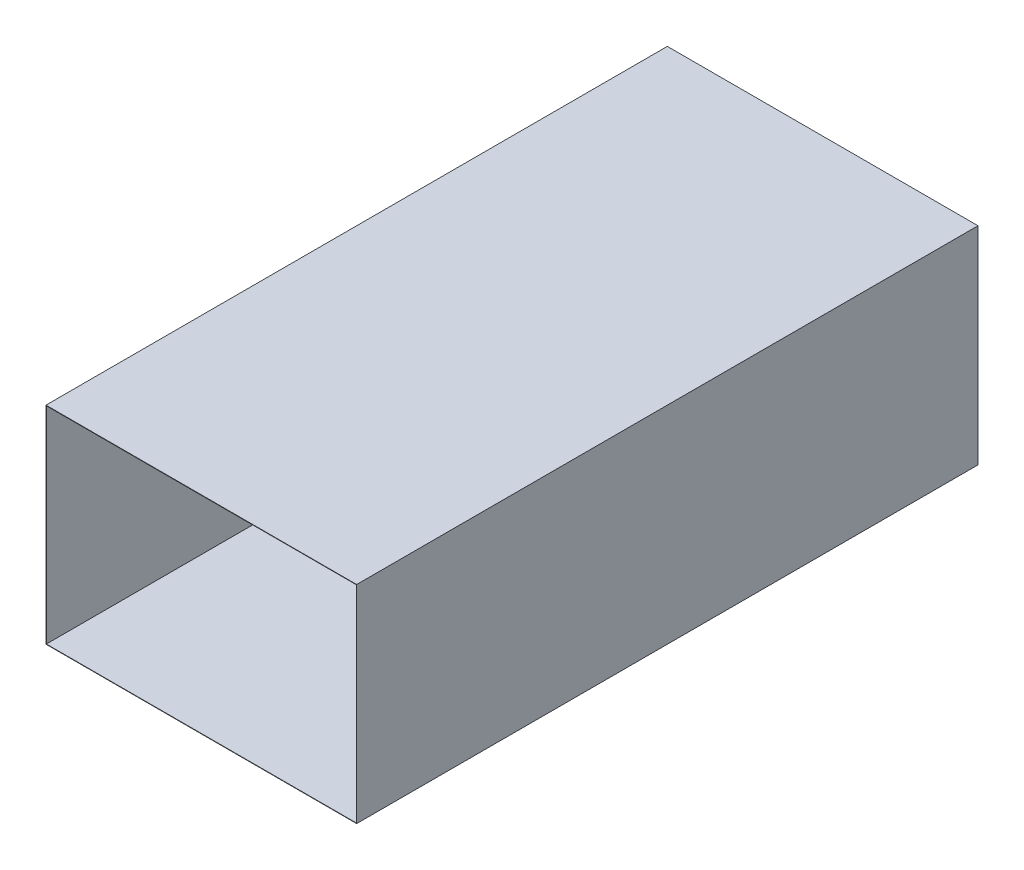
SolidWorks part; units mm, degrees
material "Plain Carbon Steel"
ref_plane "Front Plane" through (0, 0, 0) normal (0, 0, 1) x (1, 0, 0)
ref_plane "Top Plane" through (0, 0, 0) normal (0, 1, 0) x (1, 0, 0)
ref_plane "Right Plane" through (0, 0, 0) normal (1, 0, 0) x (0, 0, -1)
sketch "DuctSketch" plane through (0, 0, 0) normal (0, 0, 1) x (1, 0, 0)
  line L1 (-750, 500) -> (750, 500)
  line L2 (-750, 500) -> (-750, -500)
  line L3 (-750, -500) -> (750, -500)
  line L4 (750, 500) -> (750, -500)
  line L5 (-750, 500) -> (750, -500) construction
  line L6 (-750, -500) -> (750, 500) construction
  point P0 (0, 0)
  dimension "Height" = 1000
  dimension "Width" = 1500
extrude "Extrusion" add sketch "DuctSketch" along normal blind 3000 thin thin type one direction reverse wall 2
sketch "FilterSketch" plane through (0, 0, 0) normal (0, 0, -1) x (-1, 0, 0)
  line L1 (-750, -500) -> (750, -500)
  line L2 (-750, -500) -> (-750, 500)
  line L3 (-750, 500) -> (750, 500)
  line L4 (750, -500) -> (750, 500)
  dimension "NominalHeight" = 1000
  dimension "NominalWidth" = 1500
sketch "Sketch1" plane through (0, 0, 0) normal (0, 0, 1) x (1, 0, 0)
  point P0 (0, 0)
ref_axis "Axis1" through (0, 0, 0) along (0, 0, -1)
other "CPoint1" parameters "Diameter"=0, "StubLength"=1000
ref_axis "Axis2" through (0, 0, -10) along (0, 0, 1)
